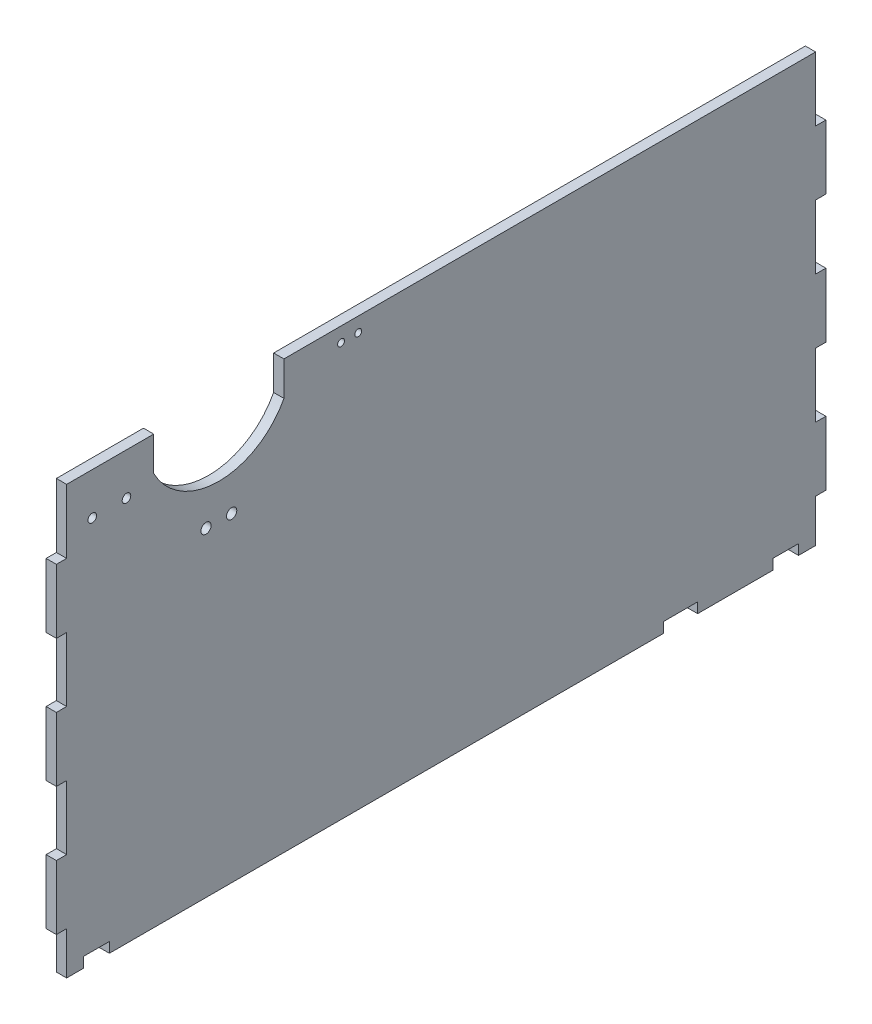
SolidWorks part; units mm, degrees
ref_plane "Front" through (0, 0, 0) normal (0, 0, 1) x (1, 0, 0)
ref_plane "Top" through (0, 0, 0) normal (0, 1, 0) x (1, 0, 0)
ref_plane "Right" through (0, 0, 0) normal (1, 0, 0) x (0, 0, -1)
sketch "Sketch1" plane through (0, 0, 0) normal (1, 0, 0) x (0, 0, -1)
  line L1 (0, 0) -> (-450, 0)
  line L2 (0, 0) -> (0, 250)
  line L3 (0, 250) -> (-450, 250)
  line L4 (-450, 0) -> (-450, 250)
  dimension "D1" = 450
  dimension "D2" = 250
extrude "Boss-Extrude1" add sketch "Sketch1" along normal blind 6
sketch "Sketch2" plane through (6, 0, 0) normal (1, 0, 0) x (0, 0, -1)
  line L0 (-450, 250) -> (-450, 0) construction
  line L1 (-450, 250) -> (-444, 250)
  line L2 (-450, 250) -> (-450, 212.5)
  line L3 (-450, 212.5) -> (-444, 212.5)
  line L4 (-444, 250) -> (-444, 212.5)
  line L5 (0, 250) -> (-450, 250) construction
  dimension "D1" = 6
  dimension "D2" = 37.5
extrude "Cut-Extrude1" cut sketch "Sketch2" against normal through all
pattern_linear "LPattern1" count 4 spacing 75 along (0, -1, 0) count 2 spacing 444 along (0, 0, -1) of "Cut-Extrude1"
sketch "Sketch3" plane through (6, 0, 0) normal (1, 0, 0) x (0, 0, -1)
  line L0 (-444, 0) -> (-6, 0) construction
  line L1 (-434, 0) -> (-419, 0)
  line L2 (-434, 0) -> (-434, 6)
  line L3 (-434, 6) -> (-419, 6)
  line L4 (-419, 0) -> (-419, 6)
  line L6 (-444, 62.5) -> (-444, 100) construction
  dimension "D1" = 10
  dimension "D2" = 15
  dimension "D3" = 6
extrude "Cut-Extrude2" cut sketch "Sketch3" against normal through all
pattern_linear "LPattern2" count 2 spacing 403 along (0, 0, -1) of "Cut-Extrude2"
sketch "Sketch4" plane through (6, 0, 0) normal (1, 0, 0) x (0, 0, -1)
  line L0 (-393.0657, 230) -> (-316.9343, 230) construction
  line L1 (-355, 250) -> (-355, 207) construction
  line L2 (-450, 212.5) -> (-450, 175) construction
  line L3 (-393.0657, 230) -> (-393.0657, 250)
  line L4 (-6, 250) -> (-444, 250) construction
  line L5 (-393.0657, 250) -> (-316.9343, 250)
  line L6 (-316.9343, 250) -> (-316.9343, 230)
  arc A0 (-393.0657, 230) -> (-316.9343, 230) centre (-355, 250) ccw
  circle A1 centre (-362.5, 187) radius 3
  circle A3 centre (-347.5, 187) radius 3
  dimension "D4" = 63
  dimension "D1" = 43
  dimension "D6" = 6
  dimension "D2" = 20
  dimension "D3" = 95
  dimension "D5" = 7.5
extrude "Cut-Extrude3" cut sketch "Sketch4" against normal blind 10
sketch "Sketch5" plane through (6, 0, 0) normal (1, 0, 0) x (0, 0, -1)
  line L0 (-419, 0) -> (-31, 0) construction
  line L1 (-75, 0) -> (-95, 0)
  line L2 (-75, 0) -> (-75, 6)
  line L3 (-75, 6) -> (-95, 6)
  line L4 (-95, 0) -> (-95, 6)
  line L5 (-16, 6) -> (-31, 6) construction
  line L6 (0, 25) -> (0, 62.5) construction
  dimension "D1" = 20
  dimension "D2" = 75
extrude "Cut-Extrude4" cut sketch "Sketch5" against normal through all
sketch "Sketch6" plane through (0, 0, 0) normal (-1, 0, 0) x (0, 0, 1)
  line L0 (444, 212.5) -> (444, 250) construction
  line L1 (6, 250) -> (316.9343, 250) construction
  line L2 (393.0657, 250) -> (444, 250) construction
  circle A0 centre (429, 225.5) radius 2.5
  circle A1 centre (409, 225.5) radius 2.5
  circle A2 centre (283.51, 241.5) radius 2
  circle A3 centre (273.51, 241.5) radius 2
  point P10 (0, 0)
  point P11 (0, 0)
  dimension "D1" = 15
  dimension "D5" = 4
  dimension "D6" = 5
  dimension "D2" = 20
  dimension "D3" = 10
  dimension "D4" = 160.49
  dimension "D7" = 8.5
  dimension "D8" = 24.5
extrude "Cut-Extrude5" cut sketch "Sketch6" against normal through all
